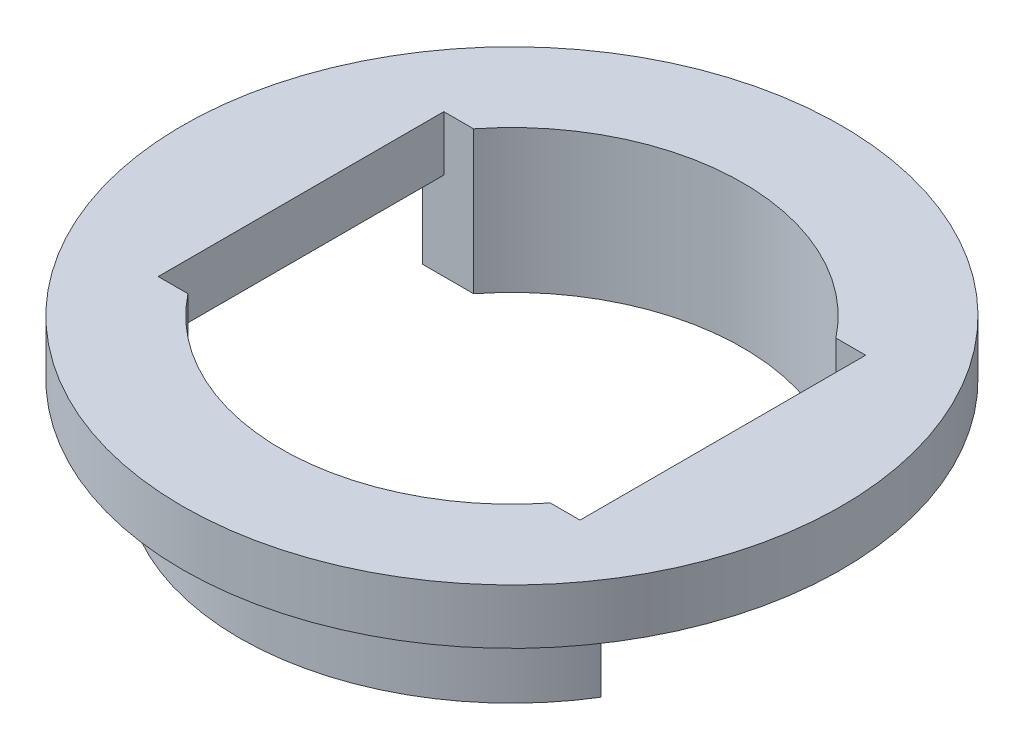
SolidWorks part; units mm, degrees
ref_plane "Front Plane" through (0, 0, 0) normal (0, 0, 1) x (1, 0, 0)
ref_plane "Top Plane" through (0, 0, 0) normal (0, 1, 0) x (1, 0, 0)
ref_plane "Right Plane" through (0, 0, 0) normal (1, 0, 0) x (0, 0, -1)
sketch "Sketch1" plane through (0, 0, 0) normal (0, 1, 0) x (1, 0, 0)
  line L0 (0, 15) -> (0, 0) construction
  line L1 (-9.6, 6.5) -> (9.6, 6.5)
  line L2 (-9.6, 6.5) -> (-9.6, -6.5)
  line L3 (-9.6, -6.5) -> (9.6, -6.5)
  line L4 (9.6, 6.5) -> (9.6, -6.5)
  line L5 (0, 0) -> (0, -15) construction
  line L6 (9.6, 6.5) -> (0, 0) construction
  line L7 (15, 0) -> (0, 0) construction
  line L8 (0, 0) -> (-15, 0) construction
  line L9 (0, 0) -> (-9.6, -6.5) construction
  line L10 (-9.6, 6.5) -> (0, 0) construction
  line L11 (0, 0) -> (9.6, -6.5) construction
  line L12 (-9.6, 6.5) -> (-13.5185, 6.5)
  line L13 (9.6, 6.5) -> (13.5185, 6.5)
  line L14 (9.6, -6.5) -> (13.5185, -6.5)
  line L15 (-9.6, -6.5) -> (-13.5185, -6.5)
  circle A0 centre (0, 0) radius 15
  dimension "D1" = 30
  dimension "D2" = 19.2
  dimension "D3" = 13
extrude "Boss-Extrude1" add sketch "Sketch1" along normal blind 2.5 contours L12 A0 L15 L2 | L15 A0 L14 L3 | L13 A0 L12 L1 | L14 A0 L13 L4 region at (0, 0, -9.999) region at (-12.0777, 0, 0) region at (12.0777, 0, 0) region at (0, 0, 9.999)
sketch "Sketch2" plane through (0, 0, 0) normal (0, -1, 0) x (1, 0, 0)
  line L0 (-21.7909, 6.5) -> (22.0222, 6.5)
  line L1 (21.3282, -6.5) -> (-23.4564, -6.5)
  circle A0 centre (0, 0) radius 12.4
  circle A1 centre (0, 0) radius 10.5
  line M6 (-9.6, 6.5) -> (9.6, 6.5)
  line M8 (9.6, -6.5) -> (-9.6, -6.5)
  dimension "D1" = 24.8
  dimension "D2" = 21
  dimension "D3" = 13
extrude "Boss-Extrude2" add sketch "Sketch2" along normal blind 4 contours A1 L0 A0 M6 | A1 L1 A0 M8 region at (0, 0, 12.1807) region at (-10.0799, 0, -6.7193)
extrude "Cut-Extrude1" cut sketch "Sketch2<3>" against normal through all both and the other way through all contours L0 A1 | L1 A1 region at (0, 0, 8.1294) region at (0, 0, -8.1294)
sketch "Sketch2<3>" plane through (0, 0, 0) normal (0, -1, 0) x (1, 0, 0) same geometry as "Sketch2"
